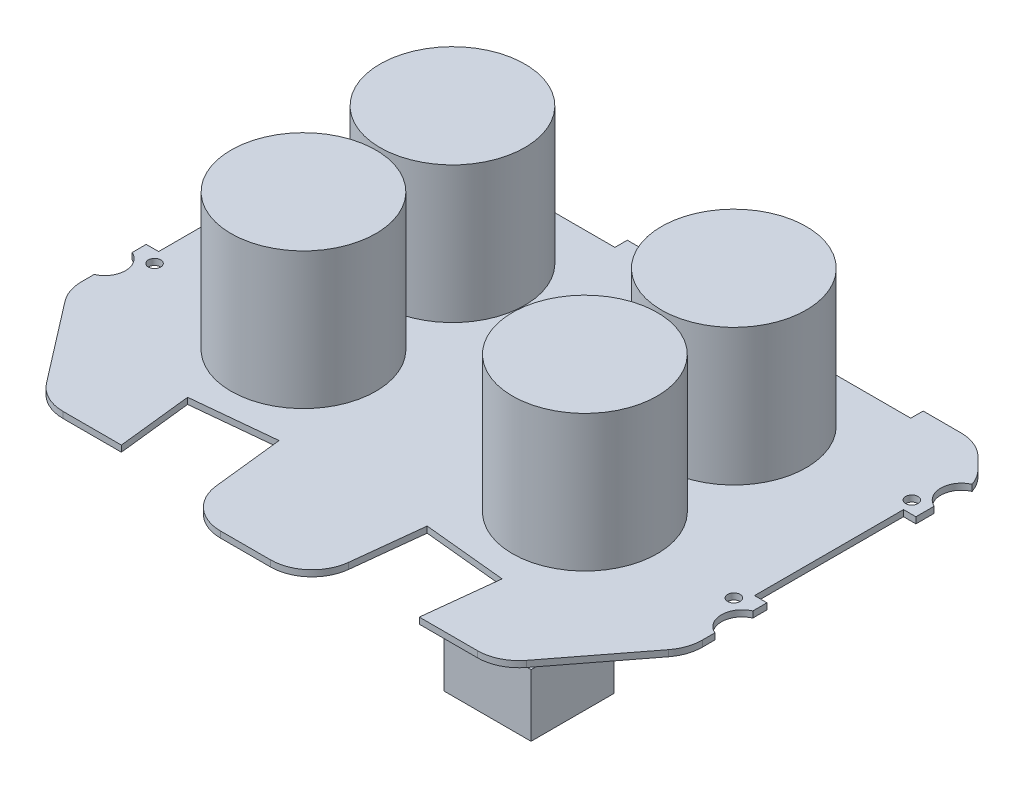
SolidWorks part; units mm, degrees
material "2A12"
ref_plane "前视基准面" through (0, 0, 0) normal (0, 0, 1) x (1, 0, 0)
ref_plane "上视基准面" through (0, 0, 0) normal (0, 1, 0) x (1, 0, 0)
ref_plane "右视基准面" through (0, 0, 0) normal (1, 0, 0) x (0, 0, -1)
sketch "草图2" plane through (0, 0, 0) normal (0, 1, 0) x (1, 0, 0)
  line L0 (242.3231, 167.0401) -> (234.3231, 159.0401)
  line L1 (234.3231, 159.0401) -> (234.3231, 89.0401)
  line L2 (384.3231, 159.0401) -> (384.3231, 89.0401)
  line L3 (254.3231, 63.0401) -> (273.3231, 63.0401)
  line L4 (294.3231, 57.0401) -> (324.3231, 57.0401)
  line L5 (384.3231, 89.0401) -> (364.3231, 63.0401)
  line L6 (234.3231, 89.0401) -> (254.3231, 63.0401)
  line L7 (273.3231, 63.0401) -> (271.3231, 81.0401)
  line L8 (271.3231, 81.0401) -> (291.4342, 83.0401)
  line L9 (291.4342, 83.0401) -> (294.3231, 57.0401)
  line L10 (364.3231, 63.0401) -> (345.3231, 63.0401)
  line L11 (345.3231, 63.0401) -> (347.3231, 81.0401)
  line L12 (347.3231, 81.0401) -> (327.212, 83.0401)
  line L13 (327.212, 83.0401) -> (324.3231, 57.0401)
  line L15 (255.5731, 167.0401) -> (291.5731, 167.0401)
  line L16 (255.5731, 167.0401) -> (255.5731, 164.0401)
  line L17 (255.5731, 164.0401) -> (291.5731, 164.0401)
  line L18 (384.3231, 159.0401) -> (376.3231, 167.0401)
  line L19 (376.3231, 167.0401) -> (242.3231, 167.0401)
  line L20 (291.5731, 167.0401) -> (291.5731, 164.0401)
  line L21 (298.0731, 167.0401) -> (320.5731, 167.0401)
  line L22 (298.0731, 167.0401) -> (298.0731, 164.0401)
  line L23 (298.0731, 164.0401) -> (320.5731, 164.0401)
  line L24 (320.5731, 167.0401) -> (320.5731, 164.0401)
  line L25 (363.0731, 167.0401) -> (327.0731, 167.0401)
  line L26 (363.0731, 167.0401) -> (363.0731, 164.0401)
  line L27 (363.0731, 164.0401) -> (327.0731, 164.0401)
  line L28 (327.0731, 167.0401) -> (327.0731, 164.0401)
  line L29 (234.3231, 144.0401) -> (237.3231, 144.0401)
  line L30 (234.3231, 144.0401) -> (234.3231, 108.0401)
  line L31 (234.3231, 108.0401) -> (237.3231, 108.0401)
  line L32 (237.3231, 144.0401) -> (237.3231, 108.0401)
  line L33 (384.3231, 144.0401) -> (381.3231, 144.0401)
  line L34 (384.3231, 144.0401) -> (384.3231, 108.0401)
  line L35 (384.3231, 108.0401) -> (381.3231, 108.0401)
  line L36 (381.3231, 144.0401) -> (381.3231, 108.0401)
  circle A0 centre (309.3231, 127.0401) radius 85
  circle A1 centre (380.3231, 147.0401) radius 1.5
  circle A2 centre (379.3231, 105.052) radius 1.5
  circle A3 centre (238.3231, 147.0401) radius 1.5
  circle A4 centre (239.3231, 105.052) radius 1.5
  circle A5 centre (386.3231, 153.0401) radius 5
  circle A6 centre (386.3231, 100.0401) radius 5
  circle A7 centre (232.3231, 153.0401) radius 5
  circle A8 centre (232.3231, 100.0401) radius 5
  dimension "D3" = 170
  dimension "D4" = 70
  dimension "D16" = 20
  dimension "D17" = 71
  dimension "D13" = 42
  dimension "D14" = 20
  dimension "D15" = 42
  dimension "D18" = 71
  dimension "D19" = 3
  dimension "D20" = 3
  dimension "D21" = 3
  dimension "D22" = 3
  dimension "D23" = 70
  dimension "D25" = 10
  dimension "D26" = 10
  dimension "D27" = 10
  dimension "D28" = 10
  dimension "D24" = 70
  dimension "D30" = 27
  dimension "D31" = 77
  dimension "D29" = 26
  dimension "D32" = 26
  dimension "D33" = 77
  dimension "D34" = 77
  dimension "D35" = 27
  dimension "D36" = 77
  dimension "D37" = 39
  dimension "D5" = 8
  dimension "D6" = 8
  dimension "D7" = 8
  dimension "D8" = 8
  dimension "D9" = 39
  dimension "D10" = 40
  dimension "D11" = 55
  dimension "D12" = 55
  dimension "D38" = 18
  dimension "D39" = 20
  dimension "D40" = 75
  dimension "D41" = 70
  dimension "D42" = 64
  dimension "D43" = 15
  dimension "D44" = 30
  dimension "D45" = 20
  dimension "D46" = 36
  dimension "D47" = 3
  dimension "D48" = 21.25
  dimension "D49" = 6.5
  dimension "D50" = 3
  dimension "D51" = 22.5
  dimension "D52" = 6.5
  dimension "D53" = 36
  dimension "D54" = 3
  dimension "D55" = 36
  dimension "D56" = 3
  dimension "D57" = 23
  dimension "D58" = 36
  dimension "D59" = 3
  dimension "D60" = 23
  dimension "D61" = 18
  dimension "D62" = 360
  dimension "D63" = 37
  dimension "D65" = 37
  dimension "D66" = 64
  dimension "D67" = 70
  dimension "D68" = 360
extrude "凸台-拉伸1" add sketch "草图2" along normal blind 1.5 contours A8 L1 L2 A6 A5 L18 L19 L0 A7 A4 A3 A2 A1 region at (309.3231, 0, -116.7894)
sketch "草图3" plane through (0, 1.5, 0) normal (0, 1, 0) x (1, 0, 0)
  line L0 (298.0731, 164.0401) -> (320.5731, 164.0401) construction
  line L1 (255.5731, 167.0401) -> (242.3231, 167.0401) construction
  line L2 (376.3231, 167.0401) -> (363.0731, 167.0401) construction
  circle A0 centre (275.3231, 141.0401) radius 17.5
  circle A1 centre (343.3231, 141.0401) radius 17.5
  circle A2 centre (275.3231, 105.0401) radius 17.5
  circle A3 centre (343.3231, 105.0401) radius 17.5
  point P8 (309.3231, 164.0401)
  point P11 (309.3231, 164.0401)
  dimension "D1" = 35
  dimension "D2" = 35
  dimension "D3" = 35
  dimension "D4" = 35
  dimension "D5" = 68
  dimension "D6" = 34
  dimension "D7" = 34
  dimension "D8" = 68
  dimension "D9" = 36
  dimension "D10" = 36
  dimension "D11" = 26
  dimension "D12" = 26
extrude "凸台-拉伸2" add sketch "草图3" along normal blind 33
sketch "草图4" plane through (0, 0, 0) normal (0, -1, 0) x (1, 0, 0)
  line L0 (384.3231, -108.0401) -> (384.3231, -104.6227) construction
  line L1 (368.3231, -67.0401) -> (347.3231, -67.0401)
  line L2 (368.3231, -67.0401) -> (368.3231, -87.0401)
  line L3 (368.3231, -87.0401) -> (347.3231, -87.0401)
  line L4 (347.3231, -67.0401) -> (347.3231, -87.0401)
  line L5 (376.3231, -167.0401) -> (363.0731, -167.0401) construction
  dimension "D1" = 16
  dimension "D2" = 21
  dimension "D3" = 20
  dimension "D4" = 100
extrude "凸台-拉伸3" add sketch "草图4" along normal blind 15
fillet "圆角1" radius 10 10 edges at (384.3231, 0.75, -159.0401) (376.3231, 0.75, -167.0401) (242.3231, 0.75, -167.0401) (234.3231, 0.75, -159.0401) (384.3231, 0.75, -89.0401) (364.3231, 0.75, -63.0401) (324.3231, 0.75, -57.0401) (294.3231, 0.75, -57.0401) (254.3231, 0.75, -63.0401) (234.3231, 0.75, -89.0401)
